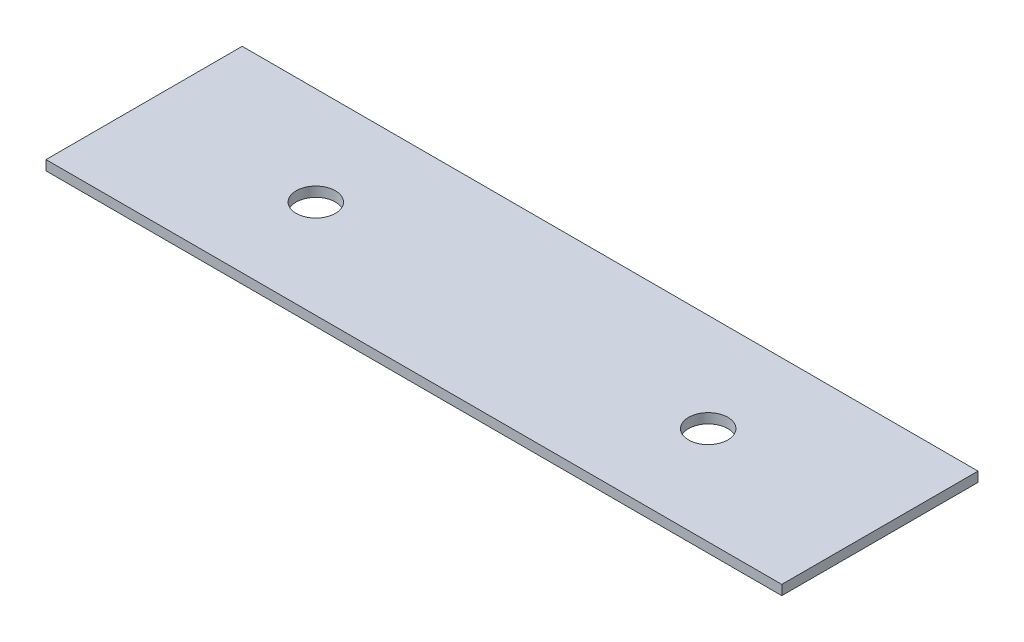
SolidWorks part; units mm, degrees
ref_plane "Front Plane" through (0, 0, 0) normal (0, 0, 1) x (1, 0, 0)
ref_plane "Top Plane" through (0, 0, 0) normal (0, 1, 0) x (1, 0, 0)
ref_plane "Right Plane" through (0, 0, 0) normal (1, 0, 0) x (0, 0, -1)
sketch "Sketch1" plane through (0, 0, 0) normal (0, 1, 0) x (1, 0, 0)
  line L1 (-75, 20) -> (75, 20)
  line L2 (-75, 20) -> (-75, -20)
  line L3 (-75, -20) -> (75, -20)
  line L4 (75, 20) -> (75, -20)
  line L5 (-75, 20) -> (75, -20) construction
  line L6 (-75, -20) -> (75, 20) construction
  point P0 (0, 0)
  dimension "D1" = 150
  dimension "D2" = 40
sheet metal parameters "Sheet-Metal1" thickness 2 parameters "D1"=0.7366
base flange "Base-Flange1" sketch "Sketch1" thickness 2 reverse thickness direction no parameters "D1"=0.7366
sketch "Sketch4" plane through (0, 0, 0) normal (0, 1, 0) x (1, 0, 0)
  line L0 (0, 20) -> (0, -20) construction
  line L1 (75, 20) -> (-75, 20) construction
  line L2 (-75, -20) -> (75, -20) construction
  line L3 (-40, 0) -> (0, 0) construction
  circle A0 centre (-40, 0) radius 4
  circle A1 centre (40, 0) radius 4
  dimension "D1" = 8
  dimension "D2" = 80
extrude "Cut-Extrude1" cut sketch "Sketch4" against normal blind 2 normal cut yes
flat pattern "Flat-Pattern1" [suppressed]
sketch "Bend-Lines1" plane through (0, 0, 0) normal (0, 1, 0) x (1, 0, 0)
  point P0 (16.9282, -47.3552)
  point P1 (75, -47.3552)
  point P2 (16.9282, -33.3639)
  point P3 (75, -33.3639)
  point P4 (27.5, -47.3552)
  point P5 (52.5, -47.3552)
  point P6 (27.5, -33.3639)
  point P7 (52.5, -33.3639)
sketch3d "Bounding-Box1" [suppressed]
  line L0 (75, -77.9825, 0) -> (-75, -77.9825, 0) construction
  line L1 (75, 20, 0) -> (-75, 20, 0) construction
  line L2 (75, -77.9825, 0) -> (75, 20, 0) construction
  line L3 (-75, -77.9825, 0) -> (-75, 20, 0) construction
